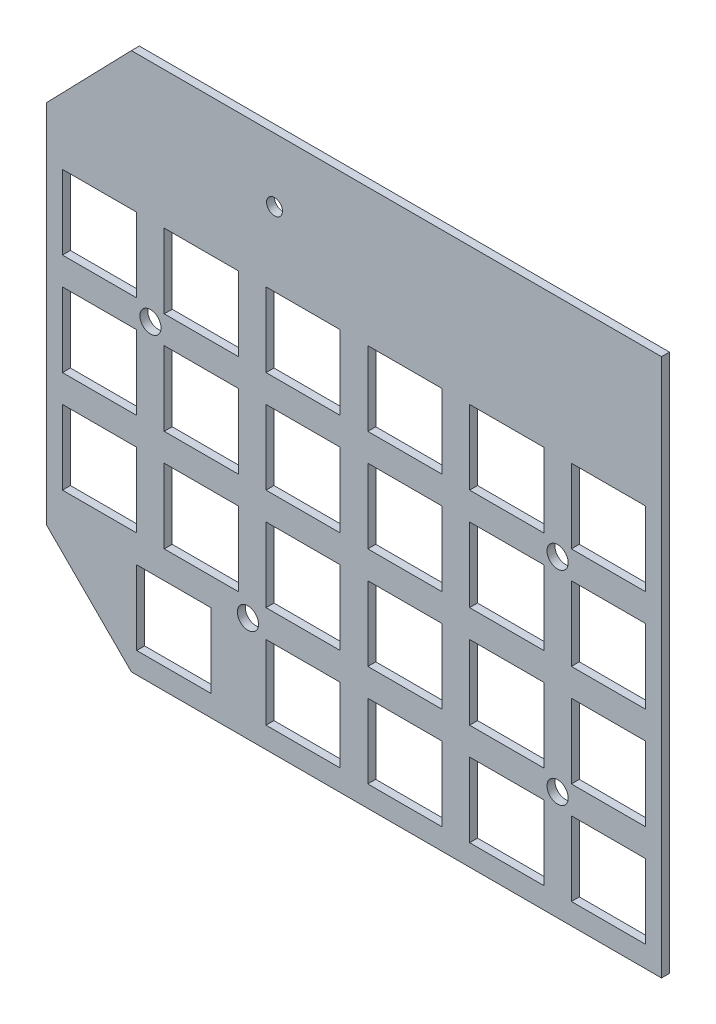
SolidWorks part; units mm, degrees
ref_plane "Plan de face" through (0, 0, 0) normal (0, 0, 1) x (1, 0, 0)
ref_plane "Plan de dessus" through (0, 0, 0) normal (0, 1, 0) x (1, 0, 0)
ref_plane "Plan de droite" through (0, 0, 0) normal (1, 0, 0) x (0, 0, -1)
sketch "Esquisse1" plane through (0, 0, 0) normal (0, 0, 1) x (1, 0, 0)
  line L0 (0, -85) -> (16, -101)
  line L4 (116, 0.5) -> (116, -101)
  line L5 (16, 0.5) -> (0, -16)
  line L7 (116, 0.5) -> (16, 0.5)
  line L8 (0, -16) -> (0, -85)
  line L9 (16, -101) -> (116, -101)
  dimension "D1" = 101.5
  dimension "D2" = 116
  dimension "D3" = 16
  dimension "D4" = 16
  dimension "D5" = 16
  dimension "D6" = 16
extrude "Boss.-Extru.1" add sketch "Esquisse1" along normal blind 1.5
sketch "Esquisse3" plane through (0, 0, 0) normal (0, 0, -1) x (-1, 0, 0)
  line L0 (-93.8, -25.4) -> (-93.8, -39.4)
  line L1 (-113, -25.4) -> (-99, -25.4)
  line L2 (-113, -25.4) -> (-113, -39.4)
  line L3 (-113, -39.4) -> (-99, -39.4)
  line L4 (-99, -25.4) -> (-99, -39.4)
  line L5 (-106, -39.4) -> (-106, -25.4) construction
  line L6 (-113, -32.4) -> (-99, -32.4) construction
  line L7 (-93.8, -25.4) -> (-79.8, -25.4)
  line L8 (-79.8, -25.4) -> (-79.8, -39.4)
  line L9 (-93.8, -39.4) -> (-79.8, -39.4)
  line L10 (-74.6, -25.4) -> (-74.6, -39.4)
  line L11 (-74.6, -25.4) -> (-60.6, -25.4)
  line L12 (-60.6, -25.4) -> (-60.6, -39.4)
  line L13 (-74.6, -39.4) -> (-60.6, -39.4)
  line L14 (-55.4, -25.4) -> (-55.4, -39.4)
  line L15 (-55.4, -25.4) -> (-41.4, -25.4)
  line L16 (-41.4, -25.4) -> (-41.4, -39.4)
  line L17 (-55.4, -39.4) -> (-41.4, -39.4)
  line L18 (-36.2, -25.4) -> (-36.2, -39.4)
  line L19 (-36.2, -25.4) -> (-22.2, -25.4)
  line L20 (-22.2, -25.4) -> (-22.2, -39.4)
  line L21 (-36.2, -39.4) -> (-22.2, -39.4)
  line L22 (-17, -25.4) -> (-17, -39.4)
  line L23 (-17, -25.4) -> (-3, -25.4)
  line L24 (-3, -25.4) -> (-3, -39.4)
  line L25 (-17, -39.4) -> (-3, -39.4)
  line L26 (-93.8, -44.6) -> (-93.8, -58.6)
  line L27 (-93.8, -44.6) -> (-79.8, -44.6)
  line L28 (-79.8, -44.6) -> (-79.8, -58.6)
  line L29 (-93.8, -58.6) -> (-79.8, -58.6)
  line L30 (-74.6, -44.6) -> (-74.6, -58.6)
  line L31 (-74.6, -44.6) -> (-60.6, -44.6)
  line L32 (-60.6, -44.6) -> (-60.6, -58.6)
  line L33 (-74.6, -58.6) -> (-60.6, -58.6)
  line L34 (-55.4, -44.6) -> (-55.4, -58.6)
  line L35 (-55.4, -44.6) -> (-41.4, -44.6)
  line L36 (-41.4, -44.6) -> (-41.4, -58.6)
  line L37 (-55.4, -58.6) -> (-41.4, -58.6)
  line L38 (-36.2, -44.6) -> (-36.2, -58.6)
  line L39 (-36.2, -44.6) -> (-22.2, -44.6)
  line L40 (-22.2, -44.6) -> (-22.2, -58.6)
  line L41 (-36.2, -58.6) -> (-22.2, -58.6)
  line L42 (-17, -44.6) -> (-17, -58.6)
  line L43 (-17, -44.6) -> (-3, -44.6)
  line L44 (-3, -44.6) -> (-3, -58.6)
  line L45 (-17, -58.6) -> (-3, -58.6)
  line L46 (-93.8, -63.8) -> (-93.8, -77.8)
  line L47 (-93.8, -63.8) -> (-79.8, -63.8)
  line L48 (-79.8, -63.8) -> (-79.8, -77.8)
  line L49 (-93.8, -77.8) -> (-79.8, -77.8)
  line L50 (-74.6, -63.8) -> (-74.6, -77.8)
  line L51 (-74.6, -63.8) -> (-60.6, -63.8)
  line L52 (-60.6, -63.8) -> (-60.6, -77.8)
  line L53 (-74.6, -77.8) -> (-60.6, -77.8)
  line L54 (-55.4, -63.8) -> (-55.4, -77.8)
  line L55 (-55.4, -63.8) -> (-41.4, -63.8)
  line L56 (-41.4, -63.8) -> (-41.4, -77.8)
  line L57 (-55.4, -77.8) -> (-41.4, -77.8)
  line L58 (-36.2, -63.8) -> (-36.2, -77.8)
  line L59 (-36.2, -63.8) -> (-22.2, -63.8)
  line L60 (-22.2, -63.8) -> (-22.2, -77.8)
  line L61 (-36.2, -77.8) -> (-22.2, -77.8)
  line L62 (-17, -63.8) -> (-17, -77.8)
  line L63 (-17, -63.8) -> (-3, -63.8)
  line L64 (-3, -63.8) -> (-3, -77.8)
  line L65 (-17, -77.8) -> (-3, -77.8)
  line L66 (-93.8, -83) -> (-93.8, -97)
  line L67 (-93.8, -83) -> (-79.8, -83)
  line L68 (-79.8, -83) -> (-79.8, -97)
  line L69 (-93.8, -97) -> (-79.8, -97)
  line L70 (-74.6, -83) -> (-74.6, -97)
  line L71 (-74.6, -83) -> (-60.6, -83)
  line L72 (-60.6, -83) -> (-60.6, -97)
  line L73 (-74.6, -97) -> (-60.6, -97)
  line L74 (-55.4, -83) -> (-55.4, -97)
  line L75 (-55.4, -83) -> (-41.4, -83)
  line L76 (-41.4, -83) -> (-41.4, -97)
  line L77 (-55.4, -97) -> (-41.4, -97)
  line L86 (-113, -44.6) -> (-113, -58.6)
  line L87 (-113, -44.6) -> (-99, -44.6)
  line L88 (-99, -44.6) -> (-99, -58.6)
  line L89 (-113, -58.6) -> (-99, -58.6)
  line L90 (-113, -63.8) -> (-113, -77.8)
  line L91 (-113, -63.8) -> (-99, -63.8)
  line L92 (-99, -63.8) -> (-99, -77.8)
  line L93 (-113, -77.8) -> (-99, -77.8)
  line L94 (-113, -83) -> (-113, -97)
  line L95 (-113, -83) -> (-99, -83)
  line L96 (-99, -83) -> (-99, -97)
  line L97 (-113, -97) -> (-99, -97)
  line L98 (-3, -83) -> (-3, -97) [skipped]
  line L99 (-17, -97) -> (-3, -97) [skipped]
  line L100 (-17, -83) -> (-17, -97) [skipped]
  line L101 (-17, -83) -> (-3, -83) [skipped]
  line L102 (-93.8, -83) -> (-99, -77.8) construction
  line L103 (-116, -101) -> (-116, 0.5) construction
  line L104 (-16, -101) -> (-116, -101) construction
  line L107 (-36.2, -83) -> (-22.2, -83) [skipped]
  line L108 (-22.2, -83) -> (-22.2, -97) [skipped]
  line L109 (-36.2, -83) -> (-36.2, -97) [skipped]
  line L110 (-36.2, -97) -> (-22.2, -97) [skipped]
  line L111 (0, -16) -> (0, -85) construction
  line L112 (-31, -83) -> (-17, -83)
  line L113 (-31, -83) -> (-31, -97)
  line L114 (-31, -97) -> (-17, -97)
  line L115 (-17, -83) -> (-17, -97)
  line L116 (-24, -97) -> (-24, -83) construction
  line L117 (-31, -90) -> (-17, -90) construction
  line L118 (-99, -39.4) -> (-93.8, -44.6) construction
  line L119 (-22.2, -39.4) -> (-17, -44.6) construction
  line L120 (-41.4, -77.8) -> (-34.5788, -84.6212) construction
  line L122 (-116, 0.5) -> (-16, 0.5) construction
  circle A0 centre (-96.4, -42) radius 2
  circle A1 centre (-19.6, -42) radius 2
  circle A2 centre (-37.9894, -81.2106) radius 2
  circle A3 centre (-96.4, -80.4) radius 2
  circle A5 centre (-43, -11.5) radius 1.5
  point P0 (-106, -32.4)
  point P84 (-24, -90)
  dimension "D7" = 43
  dimension "D8" = 12
  dimension "D1" = 14
  dimension "D2" = 14
  dimension "D5" = 4
  dimension "D6" = 3
  dimension "D9" = 5.2
  dimension "D10" = 14
  dimension "D11" = 14
  dimension "D12" = 17
  dimension "D13" = 5.2
  dimension "D3" = 6
  dimension "D4" = 4
extrude "Enlèv. mat.-Extru.2" cut sketch "Esquisse3" against normal blind 10
